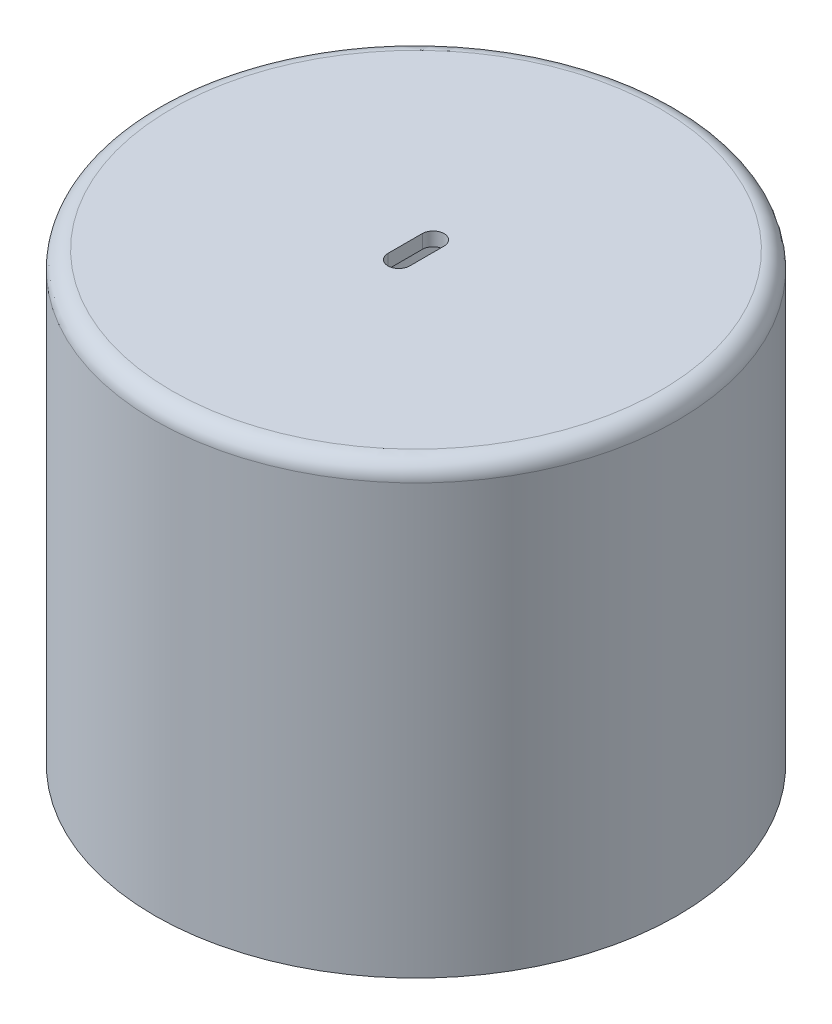
SolidWorks part; units mm, degrees
ref_plane "Front Plane" through (0, 0, 0) normal (0, 0, 1) x (1, 0, 0)
ref_plane "Top Plane" through (0, 0, 0) normal (0, 1, 0) x (1, 0, 0)
ref_plane "Right Plane" through (0, 0, 0) normal (1, 0, 0) x (0, 0, -1)
sketch "Sketch1" plane through (0, 0, 0) normal (0, 1, 0) x (1, 0, 0)
  line L0 (0, -5) -> (0, 5) construction
  line L1 (-3.175, -5) -> (-3.175, 5)
  line L2 (3.175, -5) -> (3.175, 5)
  circle A0 centre (0, 0) radius 72.2
  circle A1 centre (0, 0) radius 76.2
  arc A2 (-3.175, -5) -> (3.175, -5) centre (0, -5) ccw
  arc A3 (3.175, 5) -> (-3.175, 5) centre (0, 5) ccw
  point P6 (0, 0)
  dimension "D1" = 152.4
  dimension "D2" = 4
  dimension "D3" = 10
  dimension "D4" = 6.35
extrude "Boss-Extrude1" add sketch "Sketch1" along normal blind 130 contours A1 | L1 A3 L2 A2
extrude "Cut-Extrude1" cut sketch "Sketch1<3>" along normal offset from surface (126 mm away) 4 contours A0 region at (-70.1579, 0, 0) up to face at (0, 130, 76.2)
sketch "Sketch1<3>" plane through (0, 0, 0) normal (0, 1, 0) x (1, 0, 0) same geometry as "Sketch1"
fillet "Fillet1" radius 5 1 edges at (0, 130, 76.2)
